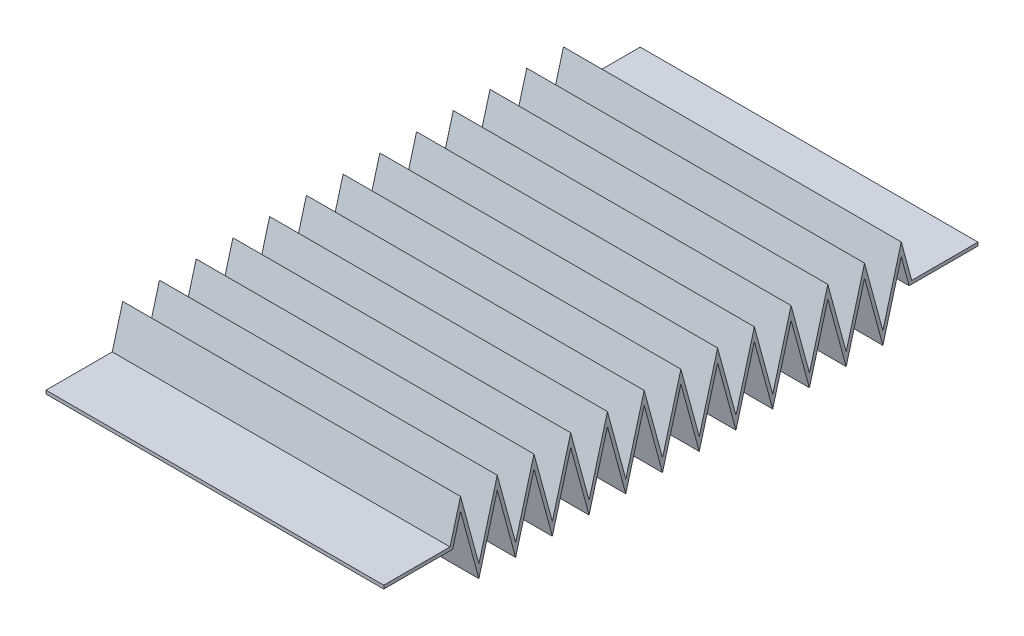
SolidWorks part; units mm, degrees
ref_plane "Front Plane" through (0, 0, 0) normal (0, 0, 1) x (1, 0, 0)
ref_plane "Top Plane" through (0, 0, 0) normal (0, 1, 0) x (1, 0, 0)
ref_plane "Right Plane" through (0, 0, 0) normal (1, 0, 0) x (0, 0, -1)
sketch "Sketch2" plane through (0, 0, 0) normal (0, 0, 1) x (1, 0, 0)
  line L1 (-27.5, 10) -> (27.5, 10)
  line L2 (-27.5, 10) -> (-27.5, 0)
  line L3 (-27.5, 0) -> (27.5, 0)
  line L4 (27.5, 10) -> (27.5, 0)
  point P4 (0, 0)
  dimension "D1" = 10
  dimension "D2" = 55
sketch "Sketch3" plane through (0, 0, 0) normal (1, 0, 0) x (0, 0, -1)
  line L0 (0, 10) -> (87.9576, 10) construction
  line L1 (0, 0) -> (87.9576, 0) construction
  line L3 (10, 5) -> (11.3592, 10)
  line L4 (11.3592, 10) -> (14.0775, 0)
  line L5 (14.0775, 0) -> (16.7958, 10)
  line L6 (16.7958, 10) -> (19.5141, 0)
  line L7 (19.5141, 0) -> (22.2324, 10)
  line L8 (22.2324, 10) -> (24.9507, 0)
  line L9 (24.9507, 0) -> (27.669, 10)
  line L10 (27.669, 10) -> (30.3873, 0)
  line L11 (30.3873, 0) -> (33.1056, 10)
  line L12 (33.1056, 10) -> (35.8239, 0)
  line L13 (35.8239, 0) -> (38.5422, 10)
  line L14 (38.5422, 10) -> (41.2605, 0)
  line L15 (41.2605, 0) -> (43.9788, 10)
  line L16 (43.9788, 10) -> (46.6971, 0)
  line L17 (46.6971, 0) -> (49.4154, 10)
  line L18 (49.4154, 10) -> (52.1337, 0)
  line L19 (0, 10) -> (0, 0) construction
  line L20 (52.1337, 0) -> (54.852, 10)
  line L21 (54.852, 10) -> (57.5703, 0)
  line L22 (57.5703, 0) -> (60.2886, 10)
  line L23 (60.2886, 10) -> (63.0069, 0)
  line L24 (63.0069, 0) -> (65.7252, 10)
  line L25 (65.7252, 10) -> (68.4435, 0)
  line L26 (68.4435, 0) -> (71.1618, 10)
  line L27 (71.1618, 10) -> (73.8801, 0)
  line L28 (73.8801, 0) -> (76.5984, 10)
  line L29 (76.5984, 10) -> (77.9576, 5)
  line L30 (87.9576, 10) -> (87.9576, 0) construction
  line L31 (10, 5) -> (0, 5)
  line L32 (77.9576, 5) -> (87.9576, 5)
  line L34 (87.9576, 22.75) -> (87.9576, 4.75) construction
  dimension "D2" = 10
  dimension "D1" = 10
  dimension "D3" = 10
extrude "Extrude-Thin1" add sketch "Sketch3" against normal mid plane 50 thin thin type mid plane wall 0.5
